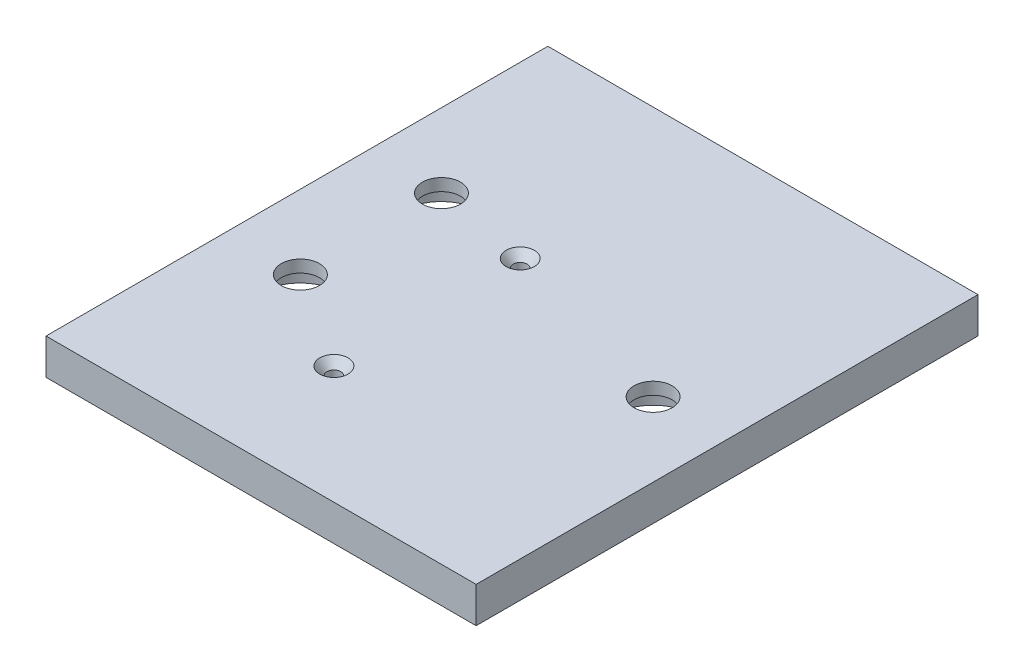
SolidWorks part; units mm, degrees
material "6061-T4 (SS)"
ref_plane "Front Plane" through (0, 0, 0) normal (0, 0, 1) x (1, 0, 0)
ref_plane "Top Plane" through (0, 0, 0) normal (0, 1, 0) x (1, 0, 0)
ref_plane "Right Plane" through (0, 0, 0) normal (1, 0, 0) x (0, 0, -1)
sketch "Sketch1" plane through (0, 0, 0) normal (0, 1, 0) x (1, 0, 0)
  line L1 (0, 0) -> (76.2, 0)
  line L2 (0, 0) -> (0, 88.9)
  line L3 (0, 88.9) -> (76.2, 88.9)
  line L4 (76.2, 0) -> (76.2, 88.9)
  dimension "D1" = 76.2
  dimension "D2" = 88.9
extrude "Boss-Extrude1" add sketch "Sketch1" along normal blind 6.35
hole_wizard "CSK for #2 Flat Head Socket Cap Screw1" positions "Sketch4" profile "Sketch5" countersink size "#2" standard "ANSI Inch"
sketch "Sketch4" plane through (0, 6.35, 0) normal (0, 1, 0) x (1, 0, 0)
  circle A0 centre (30.1, 20.9) radius 0.889 construction
  circle A1 centre (30.1, 53.9) radius 0.889 construction
  point P0 (30.1, 20.9)
  point P2 (30.1, 53.9)
  point P5 (0, 0)
  point P8 (0, 0)
sketch "Sketch5" plane through (30.1, 6.35, -20.9) normal (1, 0, 0) x (0, 0, 1)
  line L0 (0, 0) -> (0, 7.1326)
  line L1 (0, 7.1326) -> (1.2192, 6.4)
  line L2 (1.2192, 6.4) -> (1.2192, 1.4756)
  line L3 (1.2192, 1.4756) -> (2.5019, 0)
  line L5 (2.5019, 0) -> (0, 0)
  line L6 (-1.2192, 1.4756) -> (-2.5019, 0) construction
  line L10 (0, 7.1326) -> (-1.2192, 6.4) construction
  line L11 (0, -6.35) -> (0, 107.95) construction
  dimension "Hole Dia." = 2.4384
  dimension "Hole Depth" = 6.4
  dimension "Near C'Sink Dia." = 5.0038
  dimension "Near C'Sink Angle" = 82
  dimension "Drill Angle" = 118
sketch "Sketch6" plane through (0, 6.35, 0) normal (0, 1, 0) x (1, 0, 0)
  line L0 (30.1, 20.9) -> (30.1, 53.9) construction
  point P4 (30.1, 43.9)
  dimension "D1" = 10
sketch "Sketch7" plane through (0, 0, 0) normal (0, -1, 0) x (1, 0, 0)
  line L0 (38.1, 0) -> (38.1, -88.9) construction
  line L3 (0, 0) -> (76.2, 0) construction
  line L4 (76.2, -88.9) -> (0, -88.9) construction
  point P6 (38.1, -44.45)
hole_wizard "CBORE for 1/4 Binding Head Machine Screw1" positions "Sketch8" profile "Sketch9" counterbore size "1/4" standard "ANSI Inch"
sketch "Sketch8" plane through (0, 0, 0) normal (0, -1, 0) x (-1, 0, 0)
  circle A0 centre (-13.1064, 31.9532) radius 3.302 construction
  circle A1 centre (-13.1064, 56.9468) radius 3.302 construction
  circle A2 centre (-63.0936, 44.45) radius 3.302 construction
  point P0 (-63.0936, 44.45)
  point P2 (-13.1064, 31.9532)
  point P4 (-13.1064, 56.9468)
  point P9 (0, 0)
  point P12 (0, 0)
sketch "Sketch9" plane through (63.0936, 0, -44.45) normal (1, 0, 0) x (0, 0, -1)
  line L0 (0, 0) -> (0, 8.4298)
  line L1 (0, 8.4298) -> (3.3782, 6.4)
  line L2 (3.3782, 6.4) -> (3.3782, 4.191)
  line L3 (3.3782, 4.191) -> (7.1437, 4.191)
  line L4 (7.1437, 4.191) -> (7.1437, 0)
  line L5 (7.1437, 0) -> (0, 0)
  line L10 (0, 8.4298) -> (-3.3782, 6.4) construction
  line L11 (0, -6.35) -> (0, 107.95) construction
  dimension "Hole Dia." = 6.7564
  dimension "Hole Depth" = 6.4
  dimension "C'Bore Dia." = 14.2875
  dimension "C'Bore Depth" = 4.191
  dimension "Drill Angle" = 118
